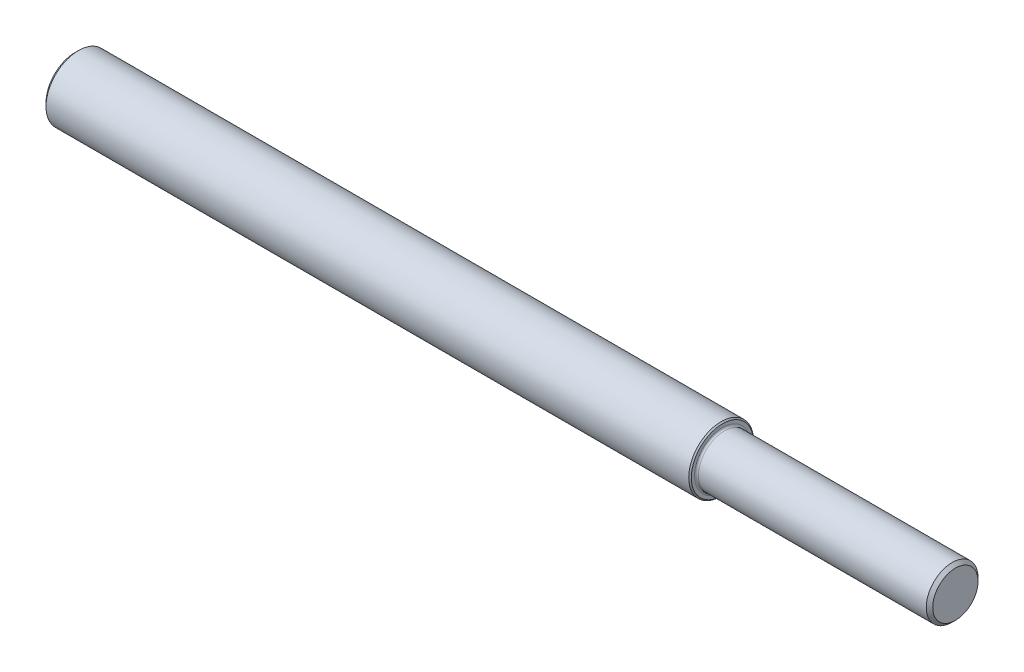
SolidWorks part; units mm, degrees
ref_plane "Front Plane" through (0, 0, 0) normal (0, 0, 1) x (1, 0, 0)
ref_plane "Top Plane" through (0, 0, 0) normal (0, 1, 0) x (1, 0, 0)
ref_plane "Right Plane" through (0, 0, 0) normal (1, 0, 0) x (0, 0, -1)
ref_plane "Plane1" through (0, 0, 0) normal (0, 0, 1) x (1, 0, 0)
sketch "Sketch1" plane through (0, 0, 0) normal (0, 0, 1) x (1, 0, 0)
  line L0 (0, 0) -> (0, 4.5)
  line L1 (0, 4.5) -> (0.5, 5)
  line L2 (0.5, 5) -> (99.8, 5)
  line L3 (99.8, 5) -> (100, 4.8)
  line L4 (100, 4.8) -> (100, 4.3)
  line L5 (100.3, 4) -> (135.5, 4)
  line L6 (135.5, 4) -> (136, 3.5)
  line L7 (136, 3.5) -> (136, 0)
  line L8 (136, 0) -> (0, 0)
  line L9 (136, 0) -> (0, 0) construction
  arc A0 (100, 4.3) -> (100.3, 4) centre (100.3, 4.3) ccw
revolve "Revolve1" add sketch "Sketch1" angle 360 about L9 reverse direction yes
